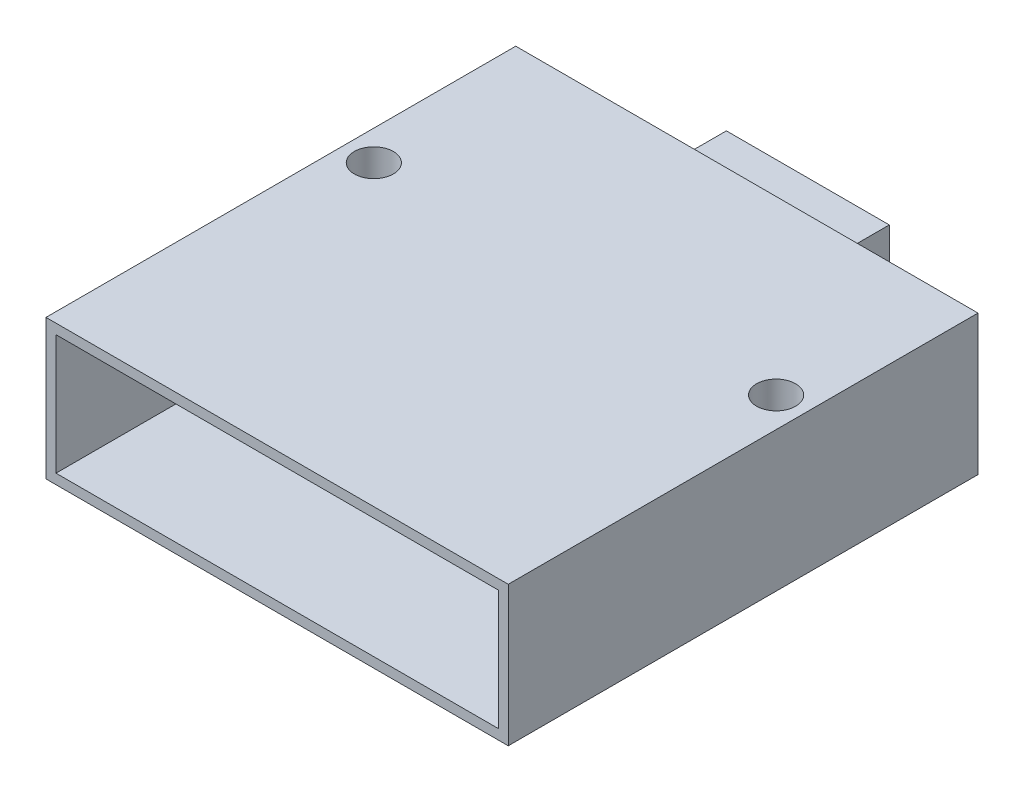
SolidWorks part; units mm, degrees
material "PVC Rigid"
ref_plane "Front Plane" through (0, 0, 0) normal (0, 0, 1) x (1, 0, 0)
ref_plane "Top Plane" through (0, 0, 0) normal (0, 1, 0) x (1, 0, 0)
ref_plane "Right Plane" through (0, 0, 0) normal (1, 0, 0) x (0, 0, -1)
sketch "Sketch1" plane through (0, 0, 0) normal (0, 0, 1) x (1, 0, 0)
  line L1 (-58.7375, -17.78) -> (58.7375, -17.78)
  line L2 (-58.7375, -17.78) -> (-58.7375, 17.78)
  line L3 (-58.7375, 17.78) -> (58.7375, 17.78)
  line L4 (58.7375, -17.78) -> (58.7375, 17.78)
  line L5 (-58.7375, -17.78) -> (58.7375, 17.78) construction
  line L6 (-58.7375, 17.78) -> (58.7375, -17.78) construction
  point P0 (0, 0)
  dimension "D1" = 117.475
  dimension "D2" = 35.56
extrude "Extrude1" add sketch "Sketch1" along normal blind 119.38
sketch "Sketch2" plane through (0, 0, 0) normal (0, 0, -1) x (-1, 0, 0)
  line L1 (-20.701, -10.414) -> (20.701, -10.414)
  line L2 (-20.701, -10.414) -> (-20.701, 10.414)
  line L3 (-20.701, 10.414) -> (20.701, 10.414)
  line L4 (20.701, -10.414) -> (20.701, 10.414)
  line L5 (-20.701, -10.414) -> (20.701, 10.414) construction
  line L6 (-20.701, 10.414) -> (20.701, -10.414) construction
  point P0 (0, 0)
  dimension "D1" = 20.828
  dimension "D2" = 41.402
extrude "Extrude2" add sketch "Sketch2" along normal blind 15.494
sketch "Sketch3" plane through (0, -17.78, 0) normal (0, -1, 0) x (1, 0, 0)
  line L0 (-51.1175, 0) -> (-51.1175, 43.688) construction
  line L1 (-58.7375, 0) -> (58.7375, 0) construction
  line L2 (-51.1175, 43.688) -> (-58.7375, 43.688) construction
  line L3 (-58.7375, 119.38) -> (-58.7375, 0) construction
  line L4 (51.1175, 0) -> (51.1175, 43.688) construction
  line L5 (51.1175, 43.688) -> (58.7375, 43.688) construction
  line L6 (58.7375, 119.38) -> (58.7375, 0) construction
  dimension "D1" = 43.688
  dimension "D2" = 7.62
hole_wizard "25/64 (0.39063) Diameter Hole1" positions "3DSketch1" profile "Sketch5" hole size "25/64" standard "Ansi Inch" end condition through all
sketch3d "3DSketch1"
  point P0 (-51.1175, -17.78, 43.688)
  point P3 (51.1175, -17.78, 43.688)
sketch "Sketch5" plane through (-51.1175, -17.78, 43.688) normal (1, 0, 0) x (0, 0, -1)
  line L0 (0, 0) -> (0, 35.56)
  line L1 (0, 35.56) -> (4.961, 35.56)
  line L2 (4.961, 35.56) -> (4.961, 0)
  line L5 (4.961, 0) -> (0, 0)
  line L11 (0, -6.35) -> (0, 107.95) construction
  dimension "Thru Hole Dia." = 9.922
  dimension "Thru Hole Depth" = 35.56
sketch "Sketch6" plane through (0, 0, -15.494) normal (0, 0, -1) x (-1, 0, 0)
  point P0 (0, 0)
sketch "Sketch7" plane through (0, 0, 119.38) normal (0, 0, 1) x (1, 0, 0)
  point P0 (0, 0)
shell "Shell1" thickness 2.54 removed face at (0, 0, 119.38)
